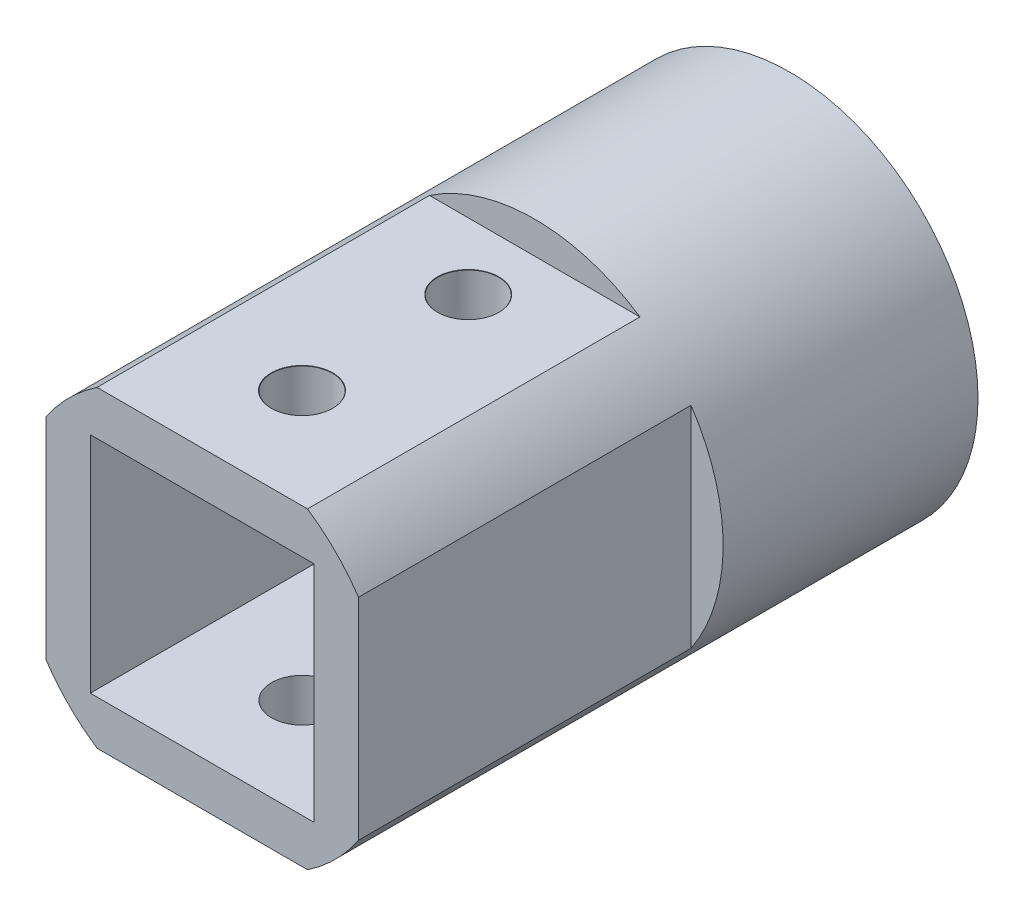
SolidWorks part; units mm, degrees
ref_plane "前视基准面" through (0, 0, 0) normal (0, 0, 1) x (1, 0, 0)
ref_plane "上视基准面" through (0, 0, 0) normal (0, 1, 0) x (1, 0, 0)
ref_plane "右视基准面" through (0, 0, 0) normal (1, 0, 0) x (0, 0, -1)
sketch "草图1" plane through (0, 0, 0) normal (0, 0, 1) x (1, 0, 0)
  circle A0 centre (0, 0) radius 17
  dimension "D1" = 34
extrude "凸台-拉伸1" add sketch "草图1" along normal blind 3
sketch "草图2" plane through (0, 0, 3) normal (0, 0, 1) x (1, 0, 0)
  circle A0 centre (0, 0) radius 17 construction
  circle A1 centre (0, 0) radius 17
  circle A2 centre (0, 0) radius 15
  dimension "D1" = 30
extrude "凸台-拉伸2" add sketch "草图2" along normal blind 10
sketch "草图3" plane through (0, 0, 3) normal (0, 0, 1) x (1, 0, 0)
  circle A0 centre (0, 0) radius 5
  dimension "D1" = 10
extrude "切除-拉伸1" cut sketch "草图3" against normal through all
sketch "草图4" plane through (0, 0, 13) normal (0, 0, 1) x (1, 0, 0)
  line L0 (0, 17) -> (0, -17) construction
  line L1 (-17, 0) -> (0, 0) construction
  line L2 (-4.4431, 10.1) -> (4.4431, 10.1)
  line L7 (10.1, 4.4431) -> (10.1, -4.4431)
  line L8 (-10.1, 4.4431) -> (-10.1, -4.4431)
  line L9 (-4.4431, 10.1) -> (-10.1, 4.4431)
  line L10 (4.4431, 10.1) -> (10.1, 4.4431)
  line L11 (-4.4431, -10.1) -> (-10.1, -4.4431)
  line L12 (-4.4431, -10.1) -> (4.4431, -10.1)
  line L13 (4.4431, -10.1) -> (10.1, -4.4431)
  circle A0 centre (0, 0) radius 17
  point P17 (0, 10.1)
  point P18 (-10.1, 0)
  point P21 (10.1, 0)
  dimension "D1" = 10.1
  dimension "D2" = 10.1
  dimension "D3" = 8
  dimension "D4" = 135
extrude "凸台-拉伸3" add sketch "草图4" along normal blind 10
sketch "草图5" plane through (0, 0, 23) normal (0, 0, 1) x (1, 0, 0)
  line L2 (-9.4968, 14.1) -> (9.4968, 14.1)
  line L4 (-14.1, 9.4968) -> (-14.1, -9.4968)
  line L6 (0, 0) -> (10.1, 10.1) construction
  line L7 (14.1, -9.4968) -> (14.1, 9.4968)
  line L8 (9.4968, -14.1) -> (-9.4968, -14.1)
  line L11 (-10.1, 10.1) -> (-10.1, -10.1)
  line L12 (-10.1, -10.1) -> (10.1, -10.1)
  line L13 (10.1, -10.1) -> (10.1, 10.1)
  line L14 (10.1, 10.1) -> (-10.1, 10.1)
  circle A1 centre (0, 0) radius 17 construction
  arc A2 (-14.1, -9.4968) -> (-9.4968, -14.1) centre (0, 0) ccw
  arc A3 (-9.4968, 14.1) -> (-14.1, 9.4968) centre (0, 0) ccw
  arc A4 (14.1404, 9.4366) -> (9.4366, 14.1404) centre (0, 0) ccw
  arc A5 (14.1, -9.4968) -> (9.4968, -14.1) centre (0, 0) cw
  circle M7 centre (0, 0) radius 17
  dimension "D1" = 4
  dimension "D2" = 4
  dimension "D3" = 20.2
  dimension "D4" = 20.2
extrude "凸台-拉伸4" add sketch "草图5" along normal blind 30 contours L6 A4 L2 L4 M7 | L6 A2 L8 L7 M7 region at (0, 13.7012, 23)
hole_wizard "M5 间隙孔2" positions "草图6" profile "草图7" hole size "M5" standard "ISO" end condition through all
sketch "草图6" plane through (0, 14.1, 0) normal (0, 1, 0) x (1, 0, 0)
  line L2 (-9.4968, -23) -> (9.4968, -23) construction
  point P0 (0, -29)
  point P2 (0, -44)
  dimension "D1" = 6
  dimension "D2" = 15
sketch "草图7" plane through (0, 14.1, 29) normal (1, 0, 0) x (0, 0, 1)
  line L0 (0, 0) -> (0, 31.1)
  line L1 (0, 31.1) -> (2.75, 31.1)
  line L2 (2.75, 31.1) -> (2.75, 0.025)
  line L3 (2.75, 0.025) -> (2.775, 0)
  line L5 (2.775, 0) -> (0, 0)
  line L6 (-2.75, 0.025) -> (-2.775, 0) construction
  line L11 (0, -6.35) -> (0, 107.95) construction
  dimension "通孔孔直径" = 5.5
  dimension "通孔孔深度" = 31.1
  dimension "近端锥形沉头孔直径" = 5.55
  dimension "近端锥形沉头孔角度" = 90
hole_wizard "M2.5 间隙孔2" positions "草图9" profile "草图10" hole size "M2.5" standard "ISO" end condition through all
sketch "草图9" plane through (0, 0, 3) normal (0, 0, 1) x (1, 0, 0)
  point P0 (8, 0)
  point P11 (8, 0)
  point P12 (8, 0)
  point P13 (8, 0)
  point P20 (0, -8)
  point P21 (-8, 0)
  point P22 (0, 8)
  dimension "D1" = 8
  dimension "D2" = 4
  dimension "D3" = 4
sketch "草图10" plane through (8, 0, 3) normal (1, 0, 0) x (0, -1, 0)
  line L0 (0, 0) -> (0, 3)
  line L1 (0, 3) -> (1.45, 3)
  line L2 (1.45, 3) -> (1.45, 0.025)
  line L3 (1.45, 0.025) -> (1.475, 0)
  line L5 (1.475, 0) -> (0, 0)
  line L6 (-1.45, 0.025) -> (-1.475, 0) construction
  line L11 (0, -6.35) -> (0, 107.95) construction
  dimension "通孔孔直径" = 2.9
  dimension "通孔孔深度" = 3
  dimension "近端锥形沉头孔直径" = 2.95
  dimension "近端锥形沉头孔角度" = 90
